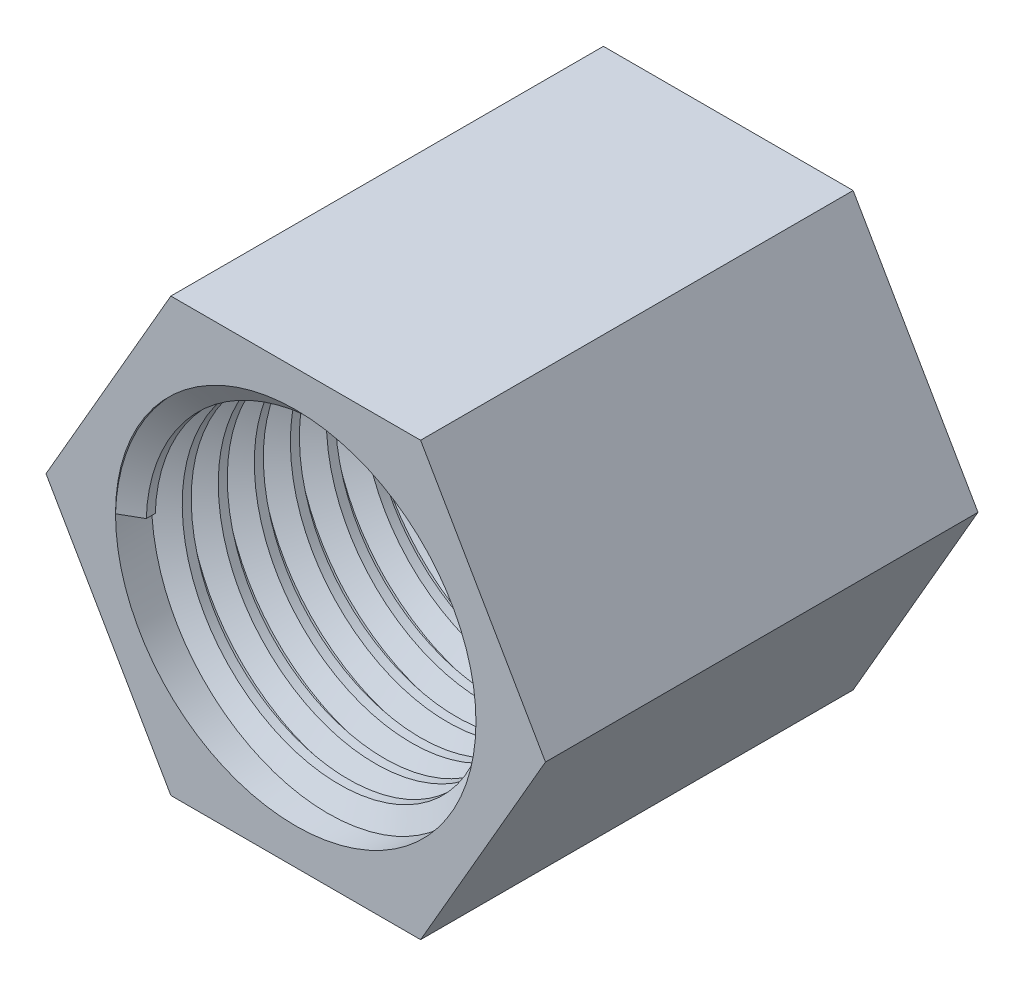
SolidWorks part; units mm, degrees
ref_plane "Front Plane" through (0, 0, 0) normal (0, 0, 1) x (1, 0, 0)
ref_plane "Top Plane" through (0, 0, 0) normal (0, 1, 0) x (1, 0, 0)
ref_plane "Right Plane" through (0, 0, 0) normal (1, 0, 0) x (0, 0, -1)
sketch "Sketch1" plane through (0, 0, 0) normal (0, 0, 1) x (1, 0, 0)
  line L1 (6.9282, 0) -> (3.4641, 6)
  line L2 (3.4641, 6) -> (-3.4641, 6)
  line L3 (-3.4641, 6) -> (-6.9282, 0)
  line L4 (-6.9282, 0) -> (-3.4641, -6)
  line L5 (-3.4641, -6) -> (3.4641, -6)
  line L6 (3.4641, -6) -> (6.9282, 0)
  circle A0 centre (0, 0) radius 6 construction
  dimension "D1" = 12
extrude "Boss-Extrude1" add sketch "Sketch1" along normal blind 12
sketch "Sketch2" plane through (0, 0, 12) normal (0, 0, 1) x (1, 0, 0)
  circle A0 centre (0, 0) radius 5
  dimension "D1" = 10
extrude "Cut-Extrude1" cut sketch "Sketch2" against normal blind 10
thread "Thread1" pitch 1 method extrude profile "Thread Profile1" start angle 0, offset 0, length 10, pitch 1, diameter 10
ref_plane "Plane1" through (-5, 0, 12) normal (0, -1, 0) x (-1, 0, 0)
sketch "Thread Profile1" plane through (-5, 0, 12) normal (0, -1, 0) x (-1, 0, 0)
  line L0 (0, 0) -> (0, 1) construction
  line L11 (0, 0) -> (0, 0.875)
  line L12 (0, 0.875) -> (-0.5413, 0.5625)
  line L13 (-0.5413, 0.5625) -> (-0.5413, 0.3125)
  line L15 (-0.5413, 0.3125) -> (0, 0)
  line L17 (-0.5413, 0.4375) -> (0, 0.4375) construction
  point P2 (0, 0)
  dimension "Pitch" = 1
  dimension "Profile_Angle" = 60
  dimension "Profile_Land" = 0.25
  dimension "Profile_Height" = 0.5413
